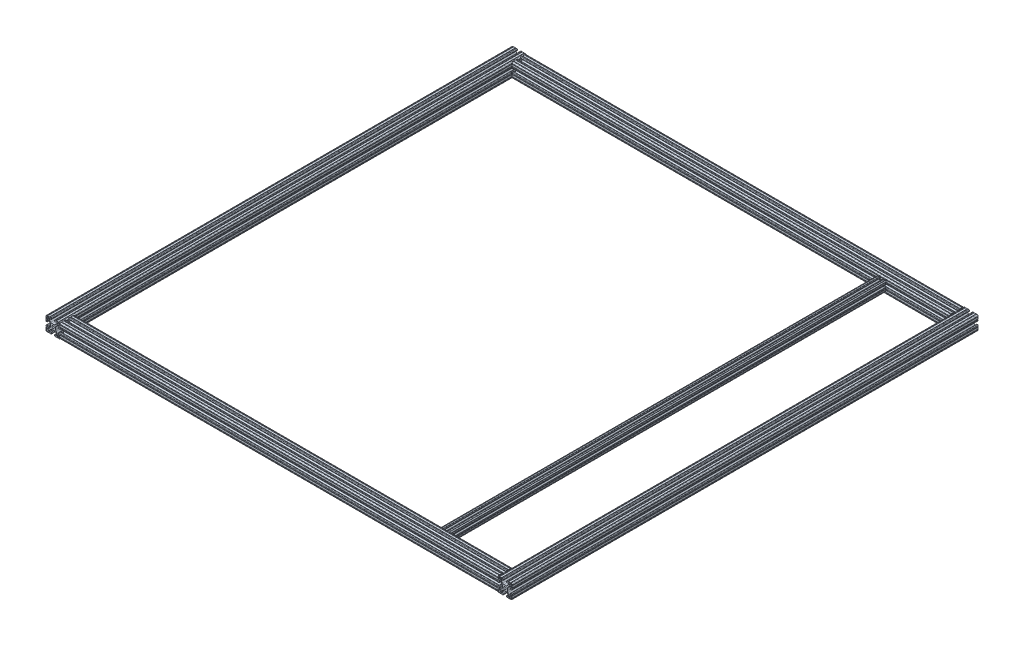
SolidWorks part; units mm, degrees
ref_plane "Front Plane" through (0, 0, 0) normal (0, 0, 1) x (1, 0, 0)
ref_plane "Top Plane" through (0, 0, 0) normal (0, 1, 0) x (1, 0, 0)
ref_plane "Right Plane" through (0, 0, 0) normal (1, 0, 0) x (0, 0, -1)
sketch3d "3DSketch1"
  line L0 (406.4, 0, -609.6) -> (406.4, 0, 609.6)
  line L1 (-609.6, 0, -609.6) -> (-609.6, 0, 609.6)
  line L2 (-609.6, 0, -609.6) -> (609.6, 0, -609.6)
  line L3 (609.6, 0, -609.6) -> (609.6, 0, 609.6)
  line L4 (-609.6, 0, 609.6) -> (609.6, 0, 609.6)
  line L5 (-609.6, 0, -609.6) -> (609.6, 0, 609.6) construction
  line L6 (609.6, 0, -609.6) -> (-609.6, 0, 609.6) construction
  point P0 (0, 0, 0)
  dimension "D1" = 1219.2
  dimension "D2" = 203.2
  dimension "D3" = 1219.2
other "Structural Member1"
ref_plane "Plane1" through (-609.6, 0, -609.6) normal (0, 0, 1) x (1, 0, 0)
sketch "Sketch111" plane through (-609.6, 0, -609.6) normal (0, 0, 1) x (1, 0, 0)
  line L0 (-11.8618, 16.8656) -> (-11.8618, 12.2428)
  line L1 (-12.2428, 11.8618) -> (-16.8656, 11.8618)
  line L2 (-17.2466, 12.2428) -> (-17.2466, 14.4526)
  line L3 (-14.4526, 17.2466) -> (-12.2428, 17.2466)
  line L4 (-16.8656, -11.8618) -> (-12.2428, -11.8618)
  line L5 (-11.8618, -12.2428) -> (-11.8618, -16.8656)
  line L6 (-12.2428, -17.2466) -> (-14.4526, -17.2466)
  line L7 (-17.2466, -14.4526) -> (-17.2466, -12.2428)
  line L8 (11.8618, -16.8656) -> (11.8618, -12.2428)
  line L9 (12.2428, -11.8618) -> (16.8656, -11.8618)
  line L10 (17.2466, -12.2428) -> (17.2466, -14.4526)
  line L11 (14.4526, -17.2466) -> (12.2428, -17.2466)
  line L12 (11.8618, 12.2428) -> (11.8618, 16.8656)
  line L13 (12.2428, 17.2466) -> (14.4526, 17.2466)
  line L14 (17.2466, 14.4526) -> (17.2466, 12.2428)
  line L15 (16.8656, 11.8618) -> (12.2428, 11.8618)
  line L16 (-14.986, 6.858) -> (-15.8242, 6.858)
  line L17 (-15.8242, 6.858) -> (-15.8242, 9.017)
  line L18 (-14.5542, 10.287) -> (-12.8105, 10.287)
  line L19 (-12.1819, 10.0266) -> (-8.2492, 6.0939)
  line L20 (-6.858, 2.7353) -> (-6.858, -2.7353)
  line L21 (-8.2492, -6.0939) -> (-12.1819, -10.0266)
  line L22 (-12.8105, -10.287) -> (-14.5542, -10.287)
  line L23 (-15.8242, -9.017) -> (-15.8242, -6.858)
  line L24 (-15.8242, -6.858) -> (-14.986, -6.858)
  line L25 (-14.986, -6.858) -> (-14.986, -5.6388)
  line L26 (-16.5608, -4.064) -> (-17.4752, -4.064)
  line L27 (-19.05, -5.6388) -> (-19.05, -7.9756)
  line L28 (-19.05, -9.4996) -> (-19.05, -14.3256)
  line L29 (-19.05, -15.8496) -> (-19.05, -16.256)
  line L30 (-16.256, -19.05) -> (-15.8496, -19.05)
  line L31 (-14.3256, -19.05) -> (-9.4996, -19.05)
  line L32 (-7.9756, -19.05) -> (-5.6388, -19.05)
  line L33 (-4.064, -17.4752) -> (-4.064, -16.5608)
  line L34 (-5.6388, -14.986) -> (-6.858, -14.986)
  line L35 (-6.858, -14.986) -> (-6.858, -15.8242)
  line L36 (-6.858, -15.8242) -> (-9.017, -15.8242)
  line L37 (-10.287, -14.5542) -> (-10.287, -12.8105)
  line L38 (-10.0266, -12.1819) -> (-6.0939, -8.2492)
  line L39 (-2.7353, -6.858) -> (2.7353, -6.858)
  line L40 (6.0939, -8.2492) -> (10.0266, -12.1819)
  line L41 (10.287, -12.8105) -> (10.287, -14.5542)
  line L42 (9.017, -15.8242) -> (6.858, -15.8242)
  line L43 (6.858, -15.8242) -> (6.858, -14.986)
  line L44 (6.858, -14.986) -> (5.6388, -14.986)
  line L45 (4.064, -16.5608) -> (4.064, -17.4752)
  line L46 (5.6388, -19.05) -> (7.9756, -19.05)
  line L47 (9.4996, -19.05) -> (14.3256, -19.05)
  line L48 (15.8496, -19.05) -> (16.256, -19.05)
  line L49 (19.05, -16.256) -> (19.05, -15.8496)
  line L50 (19.05, -14.3256) -> (19.05, -9.4996)
  line L51 (19.05, -7.9756) -> (19.05, -5.6388)
  line L52 (17.4752, -4.064) -> (16.5608, -4.064)
  line L53 (14.986, -5.6388) -> (14.986, -6.858)
  line L54 (14.986, -6.858) -> (15.8242, -6.858)
  line L55 (15.8242, -6.858) -> (15.8242, -9.017)
  line L56 (14.5542, -10.287) -> (12.8105, -10.287)
  line L57 (12.1819, -10.0266) -> (8.2492, -6.0939)
  line L58 (6.858, -2.7353) -> (6.858, 2.7353)
  line L59 (8.2492, 6.0939) -> (12.1819, 10.0266)
  line L60 (12.8105, 10.287) -> (14.5542, 10.287)
  line L61 (15.8242, 9.017) -> (15.8242, 6.858)
  line L62 (15.8242, 6.858) -> (14.986, 6.858)
  line L63 (14.986, 6.858) -> (14.986, 5.6388)
  line L64 (16.5608, 4.064) -> (17.4752, 4.064)
  line L65 (19.05, 5.6388) -> (19.05, 7.9756)
  line L66 (19.05, 9.4996) -> (19.05, 14.3256)
  line L67 (19.05, 15.8496) -> (19.05, 16.256)
  line L68 (16.256, 19.05) -> (15.8496, 19.05)
  line L69 (14.3256, 19.05) -> (9.4996, 19.05)
  line L70 (7.9756, 19.05) -> (5.6388, 19.05)
  line L71 (4.064, 17.4752) -> (4.064, 16.5608)
  line L72 (5.6388, 14.986) -> (6.858, 14.986)
  line L73 (6.858, 14.986) -> (6.858, 15.8242)
  line L74 (6.858, 15.8242) -> (9.017, 15.8242)
  line L75 (10.287, 14.5542) -> (10.287, 12.8105)
  line L76 (10.0266, 12.1819) -> (6.0939, 8.2492)
  line L77 (2.7353, 6.858) -> (-2.7353, 6.858)
  line L78 (-6.0939, 8.2492) -> (-10.0266, 12.1819)
  line L79 (-10.287, 12.8105) -> (-10.287, 14.5542)
  line L80 (-9.017, 15.8242) -> (-6.858, 15.8242)
  line L81 (-6.858, 15.8242) -> (-6.858, 14.986)
  line L82 (-6.858, 14.986) -> (-5.6388, 14.986)
  line L83 (-4.064, 16.5608) -> (-4.064, 17.4752)
  line L84 (-5.6388, 19.05) -> (-7.9756, 19.05)
  line L85 (-9.4996, 19.05) -> (-14.3256, 19.05)
  line L86 (-15.8496, 19.05) -> (-16.256, 19.05)
  line L87 (-19.05, 16.256) -> (-19.05, 15.8496)
  line L88 (-19.05, 14.3256) -> (-19.05, 9.4996)
  line L89 (-19.05, 7.9756) -> (-19.05, 5.6388)
  line L90 (-17.4752, 4.064) -> (-16.5608, 4.064)
  line L91 (-14.986, 5.6388) -> (-14.986, 6.858)
  arc A0 (-12.2428, 11.8618) -> (-11.8618, 12.2428) centre (-12.2428, 12.2428) ccw
  arc A1 (-17.2466, 12.2428) -> (-16.8656, 11.8618) centre (-16.8656, 12.2428) ccw
  arc A2 (-14.4526, 17.2466) -> (-17.2466, 14.4526) centre (-14.4526, 14.4526) ccw
  arc A3 (-11.8618, 16.8656) -> (-12.2428, 17.2466) centre (-12.2428, 16.8656) ccw
  arc A4 (-11.8618, -12.2428) -> (-12.2428, -11.8618) centre (-12.2428, -12.2428) ccw
  arc A5 (-12.2428, -17.2466) -> (-11.8618, -16.8656) centre (-12.2428, -16.8656) ccw
  arc A6 (-17.2466, -14.4526) -> (-14.4526, -17.2466) centre (-14.4526, -14.4526) ccw
  arc A7 (-16.8656, -11.8618) -> (-17.2466, -12.2428) centre (-16.8656, -12.2428) ccw
  arc A8 (12.2428, -11.8618) -> (11.8618, -12.2428) centre (12.2428, -12.2428) ccw
  arc A9 (17.2466, -12.2428) -> (16.8656, -11.8618) centre (16.8656, -12.2428) ccw
  arc A10 (14.4526, -17.2466) -> (17.2466, -14.4526) centre (14.4526, -14.4526) ccw
  arc A11 (11.8618, -16.8656) -> (12.2428, -17.2466) centre (12.2428, -16.8656) ccw
  arc A12 (12.2428, 17.2466) -> (11.8618, 16.8656) centre (12.2428, 16.8656) ccw
  arc A13 (17.2466, 14.4526) -> (14.4526, 17.2466) centre (14.4526, 14.4526) ccw
  arc A14 (16.8656, 11.8618) -> (17.2466, 12.2428) centre (16.8656, 12.2428) ccw
  arc A15 (11.8618, 12.2428) -> (12.2428, 11.8618) centre (12.2428, 12.2428) ccw
  circle A16 centre (0, 0) radius 3.3274
  arc A17 (-14.5542, 10.287) -> (-15.8242, 9.017) centre (-14.5542, 9.017) ccw
  arc A18 (-12.1819, 10.0266) -> (-12.8105, 10.287) centre (-12.8105, 9.398) ccw
  arc A19 (-6.858, 2.7353) -> (-8.2492, 6.0939) centre (-11.6078, 2.7353) ccw
  arc A20 (-8.2492, -6.0939) -> (-6.858, -2.7353) centre (-11.6078, -2.7353) ccw
  arc A21 (-12.8105, -10.287) -> (-12.1819, -10.0266) centre (-12.8105, -9.398) ccw
  arc A22 (-15.8242, -9.017) -> (-14.5542, -10.287) centre (-14.5542, -9.017) ccw
  arc A23 (-14.986, -5.6388) -> (-16.5608, -4.064) centre (-16.5608, -5.6388) ccw
  arc A24 (-17.4752, -4.064) -> (-19.05, -5.6388) centre (-17.4752, -5.6388) ccw
  arc A25 (-19.05, -9.4996) -> (-19.05, -7.9756) centre (-19.05, -8.7376) ccw
  arc A26 (-19.05, -15.8496) -> (-19.05, -14.3256) centre (-19.05, -15.0876) ccw
  arc A27 (-19.05, -16.256) -> (-16.256, -19.05) centre (-16.256, -16.256) ccw
  arc A28 (-14.3256, -19.05) -> (-15.8496, -19.05) centre (-15.0876, -19.05) ccw
  arc A29 (-7.9756, -19.05) -> (-9.4996, -19.05) centre (-8.7376, -19.05) ccw
  arc A30 (-5.6388, -19.05) -> (-4.064, -17.4752) centre (-5.6388, -17.4752) ccw
  arc A31 (-4.064, -16.5608) -> (-5.6388, -14.986) centre (-5.6388, -16.5608) ccw
  arc A32 (-10.287, -14.5542) -> (-9.017, -15.8242) centre (-9.017, -14.5542) ccw
  arc A33 (-10.0266, -12.1819) -> (-10.287, -12.8105) centre (-9.398, -12.8105) ccw
  arc A34 (-2.7353, -6.858) -> (-6.0939, -8.2492) centre (-2.7353, -11.6078) ccw
  arc A35 (6.0939, -8.2492) -> (2.7353, -6.858) centre (2.7353, -11.6078) ccw
  arc A36 (10.287, -12.8105) -> (10.0266, -12.1819) centre (9.398, -12.8105) ccw
  arc A37 (9.017, -15.8242) -> (10.287, -14.5542) centre (9.017, -14.5542) ccw
  arc A38 (5.6388, -14.986) -> (4.064, -16.5608) centre (5.6388, -16.5608) ccw
  arc A39 (4.064, -17.4752) -> (5.6388, -19.05) centre (5.6388, -17.4752) ccw
  arc A40 (9.4996, -19.05) -> (7.9756, -19.05) centre (8.7376, -19.05) ccw
  arc A41 (15.8496, -19.05) -> (14.3256, -19.05) centre (15.0876, -19.05) ccw
  arc A42 (16.256, -19.05) -> (19.05, -16.256) centre (16.256, -16.256) ccw
  arc A43 (19.05, -14.3256) -> (19.05, -15.8496) centre (19.05, -15.0876) ccw
  arc A44 (19.05, -7.9756) -> (19.05, -9.4996) centre (19.05, -8.7376) ccw
  arc A45 (19.05, -5.6388) -> (17.4752, -4.064) centre (17.4752, -5.6388) ccw
  arc A46 (16.5608, -4.064) -> (14.986, -5.6388) centre (16.5608, -5.6388) ccw
  arc A47 (14.5542, -10.287) -> (15.8242, -9.017) centre (14.5542, -9.017) ccw
  arc A48 (12.1819, -10.0266) -> (12.8105, -10.287) centre (12.8105, -9.398) ccw
  arc A49 (6.858, -2.7353) -> (8.2492, -6.0939) centre (11.6078, -2.7353) ccw
  arc A50 (8.2492, 6.0939) -> (6.858, 2.7353) centre (11.6078, 2.7353) ccw
  arc A51 (12.8105, 10.287) -> (12.1819, 10.0266) centre (12.8105, 9.398) ccw
  arc A52 (15.8242, 9.017) -> (14.5542, 10.287) centre (14.5542, 9.017) ccw
  arc A53 (14.986, 5.6388) -> (16.5608, 4.064) centre (16.5608, 5.6388) ccw
  arc A54 (17.4752, 4.064) -> (19.05, 5.6388) centre (17.4752, 5.6388) ccw
  arc A55 (19.05, 9.4996) -> (19.05, 7.9756) centre (19.05, 8.7376) ccw
  arc A56 (19.05, 15.8496) -> (19.05, 14.3256) centre (19.05, 15.0876) ccw
  arc A57 (19.05, 16.256) -> (16.256, 19.05) centre (16.256, 16.256) ccw
  arc A58 (14.3256, 19.05) -> (15.8496, 19.05) centre (15.0876, 19.05) ccw
  arc A59 (7.9756, 19.05) -> (9.4996, 19.05) centre (8.7376, 19.05) ccw
  arc A60 (5.6388, 19.05) -> (4.064, 17.4752) centre (5.6388, 17.4752) ccw
  arc A61 (4.064, 16.5608) -> (5.6388, 14.986) centre (5.6388, 16.5608) ccw
  arc A62 (10.287, 14.5542) -> (9.017, 15.8242) centre (9.017, 14.5542) ccw
  arc A63 (10.0266, 12.1819) -> (10.287, 12.8105) centre (9.398, 12.8105) ccw
  arc A64 (2.7353, 6.858) -> (6.0939, 8.2492) centre (2.7353, 11.6078) ccw
  arc A65 (-6.0939, 8.2492) -> (-2.7353, 6.858) centre (-2.7353, 11.6078) ccw
  arc A66 (-10.287, 12.8105) -> (-10.0266, 12.1819) centre (-9.398, 12.8105) ccw
  arc A67 (-9.017, 15.8242) -> (-10.287, 14.5542) centre (-9.017, 14.5542) ccw
  arc A68 (-5.6388, 14.986) -> (-4.064, 16.5608) centre (-5.6388, 16.5608) ccw
  arc A69 (-4.064, 17.4752) -> (-5.6388, 19.05) centre (-5.6388, 17.4752) ccw
  arc A70 (-9.4996, 19.05) -> (-7.9756, 19.05) centre (-8.7376, 19.05) ccw
  arc A71 (-15.8496, 19.05) -> (-14.3256, 19.05) centre (-15.0876, 19.05) ccw
  arc A72 (-16.256, 19.05) -> (-19.05, 16.256) centre (-16.256, 16.256) ccw
  arc A73 (-19.05, 14.3256) -> (-19.05, 15.8496) centre (-19.05, 15.0876) ccw
  arc A74 (-19.05, 7.9756) -> (-19.05, 9.4996) centre (-19.05, 8.7376) ccw
  arc A75 (-19.05, 5.6388) -> (-17.4752, 4.064) centre (-17.4752, 5.6388) ccw
  arc A76 (-16.5608, 4.064) -> (-14.986, 5.6388) centre (-16.5608, 5.6388) ccw
  point P0 (0, 0)
  point P1 (0, 19.05)
  point P2 (-19.05, 19.05)
  point P250 (-19.05, 0)
  point P251 (-19.05, -19.05)
  point P252 (0, -19.05)
  point P253 (19.05, -19.05)
  point P254 (19.05, 0)
  point P255 (19.05, 19.05)
  point P256 (0, 0)
other "Structural Member2"
ref_plane "Plane3" through (406.4, 0, -609.6) normal (0, 0, 1) x (1, 0, 0)
sketch "Sketch1" plane through (406.4, 0, -609.6) normal (0, 0, 1) x (1, 0, 0)
  line L1 (12.7, 12.7) -> (-12.7, 12.7) construction
  line L2 (12.7, 12.7) -> (12.7, -12.7) construction
  line L3 (12.7, -12.7) -> (-12.7, -12.7) construction
  line L4 (-12.7, 12.7) -> (-12.7, -12.7) construction
  line L5 (12.7, 12.7) -> (-12.7, -12.7) construction
  line L6 (12.7, -12.7) -> (-12.7, 12.7) construction
  line L88 (-1.7093, -4.4958) -> (1.7093, -4.4958)
  line L89 (3.9523, -5.4237) -> (7.1797, -8.6452)
  line L90 (6.4164, -10.4902) -> (4.2875, -10.4902)
  line L91 (3.2385, -11.5392) -> (3.2385, -11.651)
  line L92 (4.2875, -12.7) -> (5.3171, -12.7)
  line L93 (6.3331, -12.7) -> (9.5504, -12.7)
  line L94 (12.7, -9.5504) -> (12.7, -6.3331)
  line L95 (12.7, -5.3171) -> (12.7, -4.2875)
  line L96 (11.651, -3.2385) -> (11.5392, -3.2385)
  line L97 (10.4902, -4.2875) -> (10.4902, -6.4021)
  line L98 (8.737, -7.1292) -> (5.4405, -3.8388)
  line L99 (4.5085, -1.5917) -> (4.5085, 1.5917)
  line L100 (5.4405, 3.8388) -> (8.737, 7.1292)
  line L101 (10.4902, 6.4021) -> (10.4902, 4.2875)
  line L102 (11.5392, 3.2385) -> (11.651, 3.2385)
  line L103 (12.7, 4.2875) -> (12.7, 5.3171)
  line L104 (12.7, 6.3331) -> (12.7, 9.5504)
  line L105 (9.5504, 12.7) -> (6.3331, 12.7)
  line L106 (5.3171, 12.7) -> (4.2875, 12.7)
  line L107 (3.2384, 11.651) -> (3.2384, 11.5392)
  line L108 (4.2875, 10.4902) -> (6.4768, 10.4902)
  line L109 (7.2072, 8.7245) -> (3.9003, 5.4237)
  line L110 (1.6573, 4.4958) -> (-1.6573, 4.4958)
  line L111 (-3.9003, 5.4237) -> (-7.2072, 8.7245)
  line L112 (-6.4768, 10.4902) -> (-4.2875, 10.4902)
  line L113 (-3.2384, 11.5392) -> (-3.2384, 11.651)
  line L114 (-4.2875, 12.7) -> (-5.3171, 12.7)
  line L115 (-6.3331, 12.7) -> (-9.5504, 12.7)
  line L116 (-12.7, 9.5504) -> (-12.7, 6.3331)
  line L117 (-12.7, 5.3171) -> (-12.7, 4.2875)
  line L118 (-11.651, 3.2385) -> (-11.5392, 3.2385)
  line L119 (-10.4902, 4.2875) -> (-10.4902, 6.4021)
  line L120 (-8.737, 7.1292) -> (-5.4405, 3.8388)
  line L121 (-4.5085, 1.5917) -> (-4.5085, -1.5917)
  line L122 (-5.4405, -3.8388) -> (-8.737, -7.1292)
  line L123 (-10.4902, -6.4021) -> (-10.4902, -4.2875)
  line L124 (-11.5392, -3.2385) -> (-11.651, -3.2385)
  line L125 (-12.7, -4.2875) -> (-12.7, -5.3171)
  line L126 (-12.7, -6.3331) -> (-12.7, -9.5504)
  line L127 (-9.5504, -12.7) -> (-6.3331, -12.7)
  line L128 (-5.3171, -12.7) -> (-4.2875, -12.7)
  line L129 (-3.2385, -11.651) -> (-3.2385, -11.5392)
  line L130 (-4.2875, -10.4902) -> (-6.4164, -10.4902)
  line L131 (-7.1797, -8.6452) -> (-3.9523, -5.4237)
  circle A1 centre (0, 0) radius 2.6035
  arc A104 (-1.7093, -4.4958) -> (-3.9523, -5.4237) centre (-1.7093, -7.6708) ccw
  arc A105 (3.9523, -5.4237) -> (1.7093, -4.4958) centre (1.7093, -7.6708) ccw
  arc A106 (6.4164, -10.4902) -> (7.1797, -8.6452) centre (6.4164, -9.4098) ccw
  arc A107 (4.2875, -10.4902) -> (3.2385, -11.5392) centre (4.2875, -11.5392) ccw
  arc A108 (3.2385, -11.651) -> (4.2875, -12.7) centre (4.2875, -11.651) ccw
  arc A109 (6.3331, -12.7) -> (5.3171, -12.7) centre (5.8251, -12.7) ccw
  arc A110 (10.5664, -12.6998) -> (9.5504, -12.7) centre (10.0584, -12.7) ccw
  arc A111 (10.5664, -12.6998) -> (12.6998, -10.5664) centre (10.5918, -10.5918) ccw
  arc A112 (12.7, -9.5504) -> (12.6998, -10.5664) centre (12.7, -10.0584) ccw
  arc A113 (12.7, -5.3171) -> (12.7, -6.3331) centre (12.7, -5.8251) ccw
  arc A114 (12.7, -4.2875) -> (11.651, -3.2385) centre (11.651, -4.2875) ccw
  arc A115 (11.5392, -3.2385) -> (10.4902, -4.2875) centre (11.5392, -4.2875) ccw
  arc A116 (8.737, -7.1292) -> (10.4902, -6.4021) centre (9.4628, -6.4021) ccw
  arc A117 (4.5085, -1.5917) -> (5.4405, -3.8388) centre (7.6835, -1.5917) ccw
  arc A118 (5.4405, 3.8388) -> (4.5085, 1.5917) centre (7.6835, 1.5917) ccw
  arc A119 (10.4902, 6.4021) -> (8.737, 7.1292) centre (9.4628, 6.4021) ccw
  arc A120 (10.4902, 4.2875) -> (11.5392, 3.2385) centre (11.5392, 4.2875) ccw
  arc A121 (11.651, 3.2385) -> (12.7, 4.2875) centre (11.651, 4.2875) ccw
  arc A122 (12.7, 6.3331) -> (12.7, 5.3171) centre (12.7, 5.8251) ccw
  arc A123 (12.6998, 10.5664) -> (12.7, 9.5504) centre (12.7, 10.0584) ccw
  arc A124 (12.6998, 10.5664) -> (10.5664, 12.6998) centre (10.5918, 10.5918) ccw
  arc A125 (9.5504, 12.7) -> (10.5664, 12.6998) centre (10.0584, 12.7) ccw
  arc A126 (5.3171, 12.7) -> (6.3331, 12.7) centre (5.8251, 12.7) ccw
  arc A127 (4.2875, 12.7) -> (3.2384, 11.651) centre (4.2875, 11.651) ccw
  arc A128 (3.2384, 11.5392) -> (4.2875, 10.4902) centre (4.2875, 11.5392) ccw
  arc A129 (7.2072, 8.7245) -> (6.4768, 10.4902) centre (6.4768, 9.4563) ccw
  arc A130 (1.6573, 4.4958) -> (3.9003, 5.4237) centre (1.6573, 7.6708) ccw
  arc A131 (-3.9003, 5.4237) -> (-1.6573, 4.4958) centre (-1.6573, 7.6708) ccw
  arc A132 (-6.4768, 10.4902) -> (-7.2072, 8.7245) centre (-6.4768, 9.4563) ccw
  arc A133 (-4.2875, 10.4902) -> (-3.2384, 11.5392) centre (-4.2875, 11.5392) ccw
  arc A134 (-3.2384, 11.651) -> (-4.2875, 12.7) centre (-4.2875, 11.651) ccw
  arc A135 (-6.3331, 12.7) -> (-5.3171, 12.7) centre (-5.8251, 12.7) ccw
  arc A136 (-10.5664, 12.6998) -> (-9.5504, 12.7) centre (-10.0584, 12.7) ccw
  arc A137 (-10.5664, 12.6998) -> (-12.6998, 10.5664) centre (-10.5918, 10.5918) ccw
  arc A138 (-12.7, 9.5504) -> (-12.6998, 10.5664) centre (-12.7, 10.0584) ccw
  arc A139 (-12.7, 5.3171) -> (-12.7, 6.3331) centre (-12.7, 5.8251) ccw
  arc A140 (-12.7, 4.2875) -> (-11.651, 3.2385) centre (-11.651, 4.2875) ccw
  arc A141 (-11.5392, 3.2385) -> (-10.4902, 4.2875) centre (-11.5392, 4.2875) ccw
  arc A142 (-8.737, 7.1292) -> (-10.4902, 6.4021) centre (-9.4628, 6.4021) ccw
  arc A143 (-4.5085, 1.5917) -> (-5.4405, 3.8388) centre (-7.6835, 1.5917) ccw
  arc A144 (-5.4405, -3.8388) -> (-4.5085, -1.5917) centre (-7.6835, -1.5917) ccw
  arc A145 (-10.4902, -6.4021) -> (-8.737, -7.1292) centre (-9.4628, -6.4021) ccw
  arc A146 (-10.4902, -4.2875) -> (-11.5392, -3.2385) centre (-11.5392, -4.2875) ccw
  arc A147 (-11.651, -3.2385) -> (-12.7, -4.2875) centre (-11.651, -4.2875) ccw
  arc A148 (-12.7, -6.3331) -> (-12.7, -5.3171) centre (-12.7, -5.8251) ccw
  arc A149 (-12.6998, -10.5664) -> (-12.7, -9.5504) centre (-12.7, -10.0584) ccw
  arc A150 (-12.6998, -10.5664) -> (-10.5664, -12.6998) centre (-10.5918, -10.5918) ccw
  arc A151 (-9.5504, -12.7) -> (-10.5664, -12.6998) centre (-10.0584, -12.7) ccw
  arc A152 (-5.3171, -12.7) -> (-6.3331, -12.7) centre (-5.8251, -12.7) ccw
  arc A153 (-4.2875, -12.7) -> (-3.2385, -11.651) centre (-4.2875, -11.651) ccw
  arc A154 (-3.2385, -11.5392) -> (-4.2875, -10.4902) centre (-4.2875, -11.5392) ccw
  arc A155 (-7.1797, -8.6452) -> (-6.4164, -10.4902) centre (-6.4164, -9.4098) ccw
  point P3 (0, 0)
  point P21 (-12.7, 0)
  point P22 (0, 12.7)
  point P25 (12.7, 0)
  point P28 (0, -12.7)
  point P30 (-12.7, -12.7)
  point P33 (12.7, -12.7)
  point P37 (12.7, 12.7)
  point P40 (-12.7, 12.7)
  point P43 (0, 0)
  dimension "D1" = 25.4
other "Trim/Extend1"
